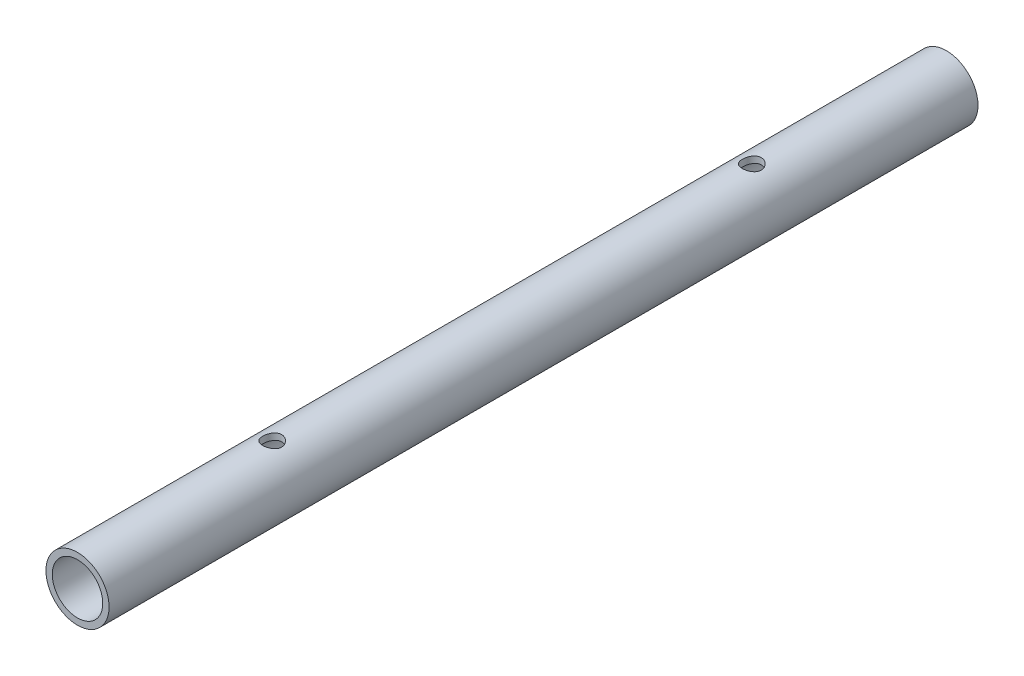
SolidWorks part; units mm, degrees
ref_plane "Plan de face" through (0, 0, 0) normal (0, 0, 1) x (1, 0, 0)
ref_plane "Plan de dessus" through (0, 0, 0) normal (0, 1, 0) x (1, 0, 0)
ref_plane "Plan de droite" through (0, 0, 0) normal (1, 0, 0) x (0, 0, -1)
sketch "Sketch1" plane through (0, 0, 0) normal (0, 0, 1) x (1, 0, 0)
  circle A0 centre (0, 0) radius 5
extrude "Boss-Extrude1" add sketch "Sketch1" along normal blind 137.657
sketch "Sketch2" plane through (0, 0, 137.657) normal (0, 0, 1) x (1, 0, 0)
  circle A0 centre (0, 0) radius 4
extrude "Cut-Extrude1" cut sketch "Sketch2" against normal up to next
sketch "Sketch5" plane through (0, 0, 0) normal (0, 1, 0) x (1, 0, 0)
  circle A0 centre (0, -30.835) radius 1.5
  circle A1 centre (0, -106.822) radius 1.5
  dimension "D1" = 30.835
  dimension "D2" = 106.822
extrude "Cut-Extrude2" cut sketch "Sketch5" against normal through all and the other way through all
